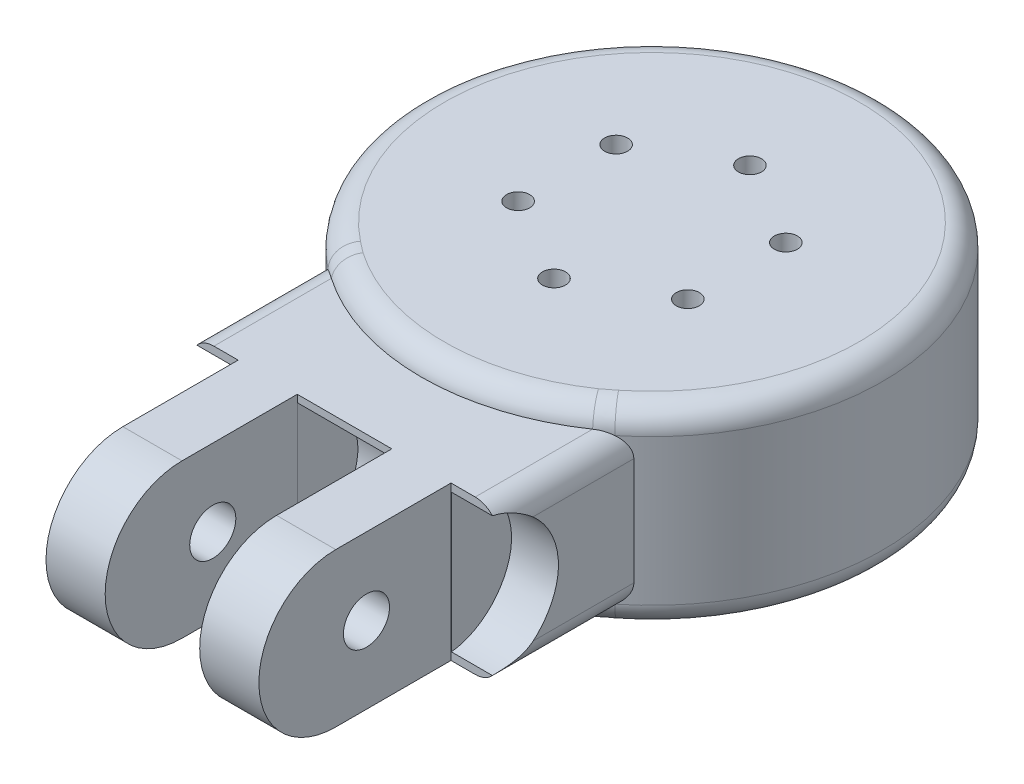
SolidWorks part; units mm, degrees
ref_plane "Front Plane" through (0, 0, 0) normal (0, 0, 1) x (1, 0, 0)
ref_plane "Top Plane" through (0, 0, 0) normal (0, 1, 0) x (1, 0, 0)
ref_plane "Right Plane" through (0, 0, 0) normal (1, 0, 0) x (0, 0, -1)
sketch "Sketch1" plane through (0, 0, 0) normal (0, 1, 0) x (1, 0, 0)
  line L1 (20, 10) -> (-20, 10)
  line L2 (20, 10) -> (20, -10)
  line L3 (20, -10) -> (-20, -10)
  line L4 (-20, 10) -> (-20, -10)
  line L5 (20, 10) -> (-20, -10) construction
  line L6 (20, -10) -> (-20, 10) construction
  point P0 (0, 0)
  dimension "D1" = 40
  dimension "D2" = 20
extrude "Boss-Extrude1" add sketch "Sketch1" along normal mid plane 20
fillet "Fillet1" radius 3 4 edges at (-20, 10, 0) (-20, -10, 0) (20, 10, 0) (20, -10, 0)
sketch "Sketch3" plane through (0, 0, 0) normal (0, 1, 0) x (1, 0, 0)
  line L0 (0, 0) -> (0, 30) construction
  circle A0 centre (0, 30) radius 30
  dimension "35" = 30
extrude "Boss-Extrude2" add sketch "Sketch3" along normal mid plane 25
fillet "Fillet2" radius 3 2 edges at (0, -12.5, 0) (0, 12.5, 0)
sketch "Sketch4" plane through (0, 0, 10) normal (0, 0, 1) x (1, 0, 0)
  line L9 (15.6, 5.6) -> (-15.6, 5.6)
  line L10 (-15.6, 5.6) -> (-15.6, -5.6)
  line L11 (-15.6, -5.6) -> (15.6, -5.6)
  line L12 (15.6, -5.6) -> (15.6, 5.6)
  line L13 (15.6, 5.6) -> (-15.6, 5.6)
  line L14 (-15.6, 5.6) -> (-15.6, -5.6)
  line L15 (-15.6, -5.6) -> (15.6, -5.6)
  line L16 (15.6, -5.6) -> (15.6, 5.6)
  dimension "D1" = 4.4
sketch "Sketch5" plane through (0, 12.5, 0) normal (0, 1, 0) x (1, 0, 0)
  line L0 (0, 0) -> (0, 182.6104) construction
  line L1 (0, 182.6104) -> (0, 30) construction
  line L2 (0, 30) -> (91.1413, 30) construction
  circle A0 centre (0, 30) radius 12.75
  circle A1 centre (0, 42.75) radius 1.5
  circle A2 centre (11.0418, 36.375) radius 1.5
  circle A3 centre (11.0418, 23.625) radius 1.5
  circle A4 centre (0, 17.25) radius 1.5
  circle A5 centre (-11.0418, 23.625) radius 1.5
  circle A6 centre (-11.0418, 36.375) radius 1.5
  point P21 (0, 30)
  dimension "D2" = 3
  dimension "D4" = 25.5
  dimension "D3" = 6
extrude "Cut-Extrude1" cut sketch "Sketch5" against normal through all contours A0 A4 | A6 | A5 | A4 | A3 | A2 | A1 region at (0, 12.5, -16.6295)
sketch "Sketch6" plane through (0, 0, 10) normal (0, 0, 1) x (1, 0, 0)
  line L0 (-17, -10) -> (17, -10) construction
  line L1 (-13.85, 10) -> (-6.15, 10)
  line L2 (-13.85, 10) -> (-13.85, -10)
  line L3 (-13.85, -10) -> (-6.15, -10)
  line L4 (-6.15, 10) -> (-6.15, -10)
  line L5 (-13.85, 10) -> (-6.15, -10) construction
  line L6 (-13.85, -10) -> (-6.15, 10) construction
  line L7 (0, -13.75) -> (0, 13.75) construction
  line L8 (13.85, -10) -> (6.15, -10)
  line L9 (6.15, 10) -> (6.15, -10)
  line L10 (13.85, 10) -> (6.15, 10)
  line L11 (13.85, 10) -> (13.85, -10)
  point P0 (-10, 0)
  dimension "D1" = 10
  dimension "D2" = 7.7
  dimension "D3" = 20
extrude "Boss-Extrude3" add sketch "Sketch6" along normal blind 25
sketch "Sketch7" plane through (-13.85, 0, 0) normal (-1, 0, 0) x (0, 0, 1)
  line L1 (35, 10) -> (35, -10) construction
  circle A0 centre (21, 0) radius 3
  dimension "D1" = 6
  dimension "12.4" = 14
extrude "Cut-Extrude3" cut sketch "Sketch7" against normal through all both and the other way through all
sketch "Sketch9" plane through (0, 0, 10) normal (0, 0, 1) x (1, 0, 0)
  line L0 (-13.85, -10) -> (-13.85, 10) construction
  line L1 (-13.85, 10) -> (-17, 10) construction
  line L2 (-20, 7) -> (-20, -7) construction
  line L3 (-17, -10) -> (-13.85, -10) construction
  line L4 (13.85, 10) -> (13.85, -10) construction
  line L5 (13.85, -10) -> (17, -10) construction
  line L6 (20, -7) -> (20, 7) construction
  line L7 (17, 10) -> (13.85, 10) construction
  line L8 (13.85, 10) -> (13.85, -10)
  line L9 (13.85, -10) -> (17, -10)
  line L10 (20, -7) -> (20, 7)
  line L11 (17, 10) -> (13.85, 10)
  line L12 (-13.85, -10) -> (-13.85, 10)
  line L13 (-13.85, 10) -> (-17, 10)
  line L14 (-20, 7) -> (-20, -7)
  line L15 (-17, -10) -> (-13.85, -10)
  line L20 (-6.15, 10) -> (-6.15, -10)
  line L21 (-6.15, -10) -> (6.15, -10)
  line L22 (6.15, -10) -> (6.15, 10)
  line L23 (6.15, 10) -> (-6.15, 10)
  line L24 (-6.15, 10) -> (-6.15, -10)
  line L25 (-6.15, -10) -> (6.15, -10)
  line L26 (6.15, -10) -> (6.15, 10)
  line L27 (6.15, 10) -> (-6.15, 10)
  arc A0 (-17, 10) -> (-20, 7) centre (-17, 7) ccw construction
  arc A1 (-20, -7) -> (-17, -10) centre (-17, -7) ccw construction
  arc A2 (17, -10) -> (20, -7) centre (17, -7) ccw construction
  arc A3 (20, 7) -> (17, 10) centre (17, 7) ccw construction
  arc A4 (17, -10) -> (20, -7) centre (17, -7) ccw
  arc A5 (20, 7) -> (17, 10) centre (17, 7) ccw
  arc A6 (-17, 10) -> (-20, 7) centre (-17, 7) ccw
  arc A7 (-20, -7) -> (-17, -10) centre (-17, -7) ccw
  dimension "D1" = 0
sketch "Sketch13" plane through (-20, 0, 0) normal (-1, 0, 0) x (0, 0, 1)
  line L0 (3.725, 4.9815) -> (3.725, -5.0434) construction
  line L4 (10, 9) -> (10, -9)
  line L5 (10, -10) -> (10, 10) construction
  line L8 (10, -10) -> (10, -7) construction
  line L9 (-5.2816, 10) -> (10, 10) construction
  line L10 (10, -10) -> (-5.2816, -10) construction
  spline S0 degree 3 poles (10, 9) (5.4072, 8.4885) (-1.1543, -0.1959) (5.5793, -8.5203) (10, -9) knots 0 0 0 0 0.509664 1 1 1 1
  point P3 (0, 0)
  point P6 (1.4504, -0.031)
  point P13 (2.1724, -0.2702)
  dimension "D1" = 1
  dimension "D2" = 1
extrude "Cut-Extrude10" cut sketch "Sketch13" against normal blind 6.1
mirror "Mirror3" about plane through (0, 0, 0) normal (1, 0, 0) of "Cut-Extrude10"
sketch "Sketch17" plane through (0, 0, 0) normal (1, 0, 0) x (0, 0, -1)
  line L0 (-4.2963, 5.3784) -> (-4.2963, -5.5398) construction
  line L1 (-10, 9.052) -> (-10, -9)
  spline S0 degree 3 poles (-10, 9.052) (-6.0906, 8.2405) (1.6776, 0.0459) (-5.9441, -8.3935) (-10, -9) knots 0 0 0 0 0.499552 1 1 1 1
  spline S1 degree 3 poles (-10, 9) (-5.4072, 8.4885) (1.1543, -0.1959) (-5.5793, -8.5203) (-10, -9) knots 0 0 0 0 0.509664 1 1 1 1 construction
  spline S2 degree 3 poles (-5.4573, -7) (-6.7185, -8.0763) (-8.274, -8.8127) (-10, -9) knots 0.808551 0.808551 0.808551 0.808551 1 1 1 1 construction
  spline S3 degree 3 poles (-5.4942, 7) (-3.3921, 5.1979) (-0.8985, -0.1297) (-3.4883, -5.3197) (-5.4573, -7) knots 0.190207 0.190207 0.190207 0.190207 0.509664 0.808551 0.808551 0.808551 0.808551 construction
  point P7 (0.3473, 30.5516)
  point P8 (11.3104, 21.8067)
  point P9 (-10, -9)
  point P14 (-2.17, -0.0079)
  point P17 (-4.2963, -5.5398)
extrude "Cut-Extrude14" cut sketch "Sketch17" along normal mid plane 12.2
fillet "Fillet5" 2 edges at (-10, 10, 35) (-10, -10, 35) type full round first side face at (0, 10, 16.2265) second side face at (0, -10, 16.2265) middle face at (-10, 0, 35)
fillet "Fillet6" 2 edges at (10, 10, 35) (10, -10, 35) type full round first side face at (0, 10, 14.5599) second side face at (0, -10, 14.5599) middle face at (10, 0, 35)
